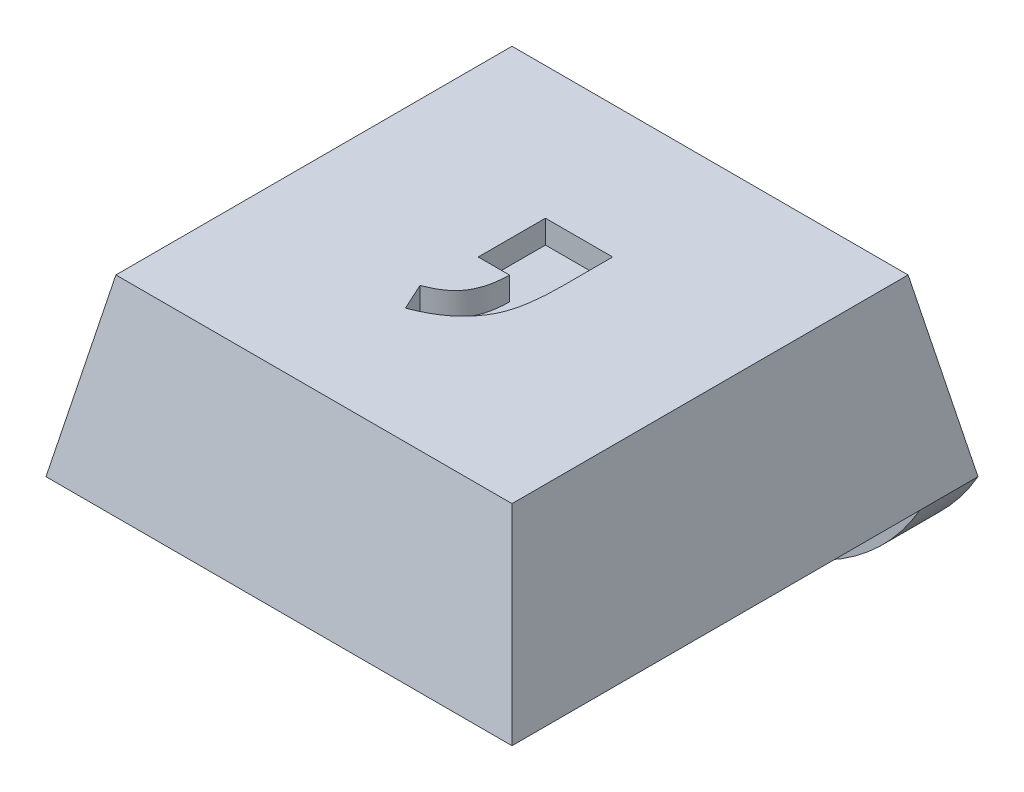
SolidWorks part; units mm, degrees
ref_plane "Front Plane" through (0, 0, 0) normal (0, 0, 1) x (1, 0, 0)
ref_plane "Top Plane" through (0, 0, 0) normal (0, 1, 0) x (1, 0, 0)
ref_plane "Right Plane" through (0, 0, 0) normal (1, 0, 0) x (0, 0, -1)
sketch "Sketch1" plane through (0, 0, 0) normal (0, 1, 0) x (1, 0, 0)
  line L1 (0, 0) -> (8, 0)
  line L2 (0, 0) -> (0, 8)
  line L3 (0, 8) -> (8, 8)
  line L4 (8, 0) -> (8, 8)
  dimension "D1" = 8
  dimension "D2" = 8
extrude "Boss-Extrude1" add sketch "Sketch1" along normal blind 3
sketch "Sketch2" plane through (0, 0, 0) normal (0, 0, 1) x (1, 0, 0)
  line L0 (0, 0) -> (0.6, 3)
  line L1 (0, 3) -> (8, 3) construction
  line L2 (0.6, 3) -> (0, 3)
  line L3 (0, 3) -> (0, 0)
  line L4 (8, 0) -> (7.4, 3)
  line L5 (7.4, 3) -> (8, 3)
  line L6 (8, 3) -> (8, 0)
  dimension "D1" = 0.6
  dimension "D2" = 0.6
extrude "Cut-Extrude1" cut sketch "Sketch2" against normal through all both and the other way through all
sketch "Sketch3" plane through (0, 0, 0) normal (1, 0, 0) x (0, 0, -1)
  line L0 (0, 0) -> (0.6, 3)
  line L1 (8, 3) -> (0, 3) construction
  line L2 (0.6, 3) -> (0, 3)
  line L3 (0, 3) -> (0, 0)
  line L4 (8, 3) -> (7.4, 3)
  line L5 (7.4, 3) -> (8, 0)
  line L6 (8, 3) -> (8, 0)
  dimension "D1" = 0.6
  dimension "D2" = 0.6
extrude "Cut-Extrude2" cut sketch "Sketch3" along normal blind 11
sketch "Sketch4" plane through (0, 0, 0) normal (0, -1, 0) x (1, 0, 0)
  line L0 (8, 0) -> (8, -8) construction
  line L3 (0, 0) -> (8, 0) construction
  circle A0 centre (4, -3.75) radius 1.75
  dimension "D1" = 3.5
  dimension "D2" = 4
  dimension "D3" = 3.75
extrude "Cut-Extrude3" cut sketch "Sketch4" against normal blind 0.4
sketch "Sketch5" plane through (0, 0, 0) normal (0, -1, 0) x (1, 0, 0)
  line L0 (8, 0) -> (8, -8) construction
  line L1 (0, -8) -> (8, -8)
  line L2 (0, -8) -> (0, -7)
  line L3 (0, -7) -> (8, -7)
  line L4 (8, -8) -> (8, -7)
  dimension "D1" = 1
extrude "Boss-Extrude2" add sketch "Sketch5" along normal blind 2
fillet "Fillet1" radius 4 2 edges at (8, -2, -7.5) (0, -2, -7.5)
sketch "Sketch6" plane through (0, 3, 0) normal (0, 1, 0) x (1, 0, 0)
  text T0 "," font "Arial" height 6
extrude "Cut-Extrude4" cut sketch "Sketch6" against normal blind 0.4
